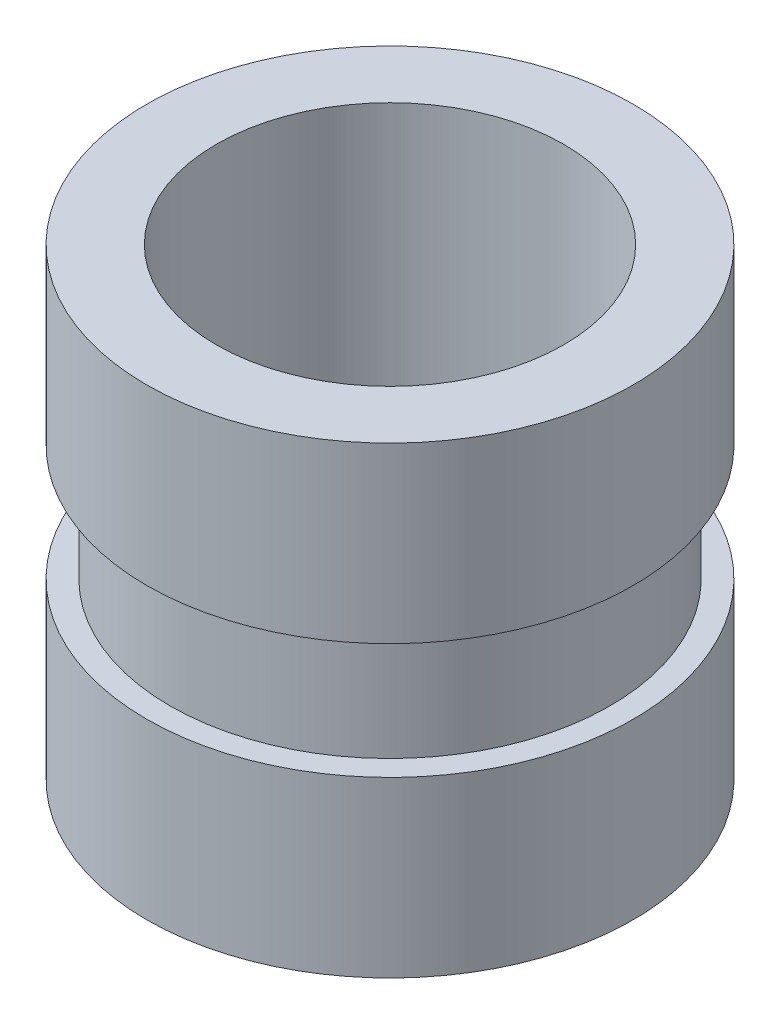
SolidWorks part; units mm, degrees
ref_plane "Front Plane" through (0, 0, 0) normal (0, 0, 1) x (1, 0, 0)
ref_plane "Top Plane" through (0, 0, 0) normal (0, 1, 0) x (1, 0, 0)
ref_plane "Right Plane" through (0, 0, 0) normal (1, 0, 0) x (0, 0, -1)
sketch "Sketch1" plane through (0, 0, 0) normal (0, 0, 1) x (1, 0, 0)
  line L0 (1.5, 0) -> (2.1, 0)
  line L1 (2.1, 0) -> (2.1, 1.5)
  line L2 (2.1, 1.5) -> (1.9, 1.5)
  line L3 (1.9, 1.5) -> (1.9, 2.5)
  line L4 (1.9, 2.5) -> (2.1, 2.5)
  line L5 (2.1, 2.5) -> (2.1, 4)
  line L6 (2.1, 4) -> (1.5, 4)
  line L7 (1.5, 4) -> (1.5, 0)
  line L8 (0, 4.902) -> (0, -1.8868) construction
  dimension "D1" = 1.5
  dimension "D2" = 1.5
  dimension "D3" = 4
  dimension "D4" = 0.2
  dimension "D5" = 1.5
  dimension "D6" = 2.1
revolve "Revolve1" add sketch "Sketch1" angle 360 about L8
